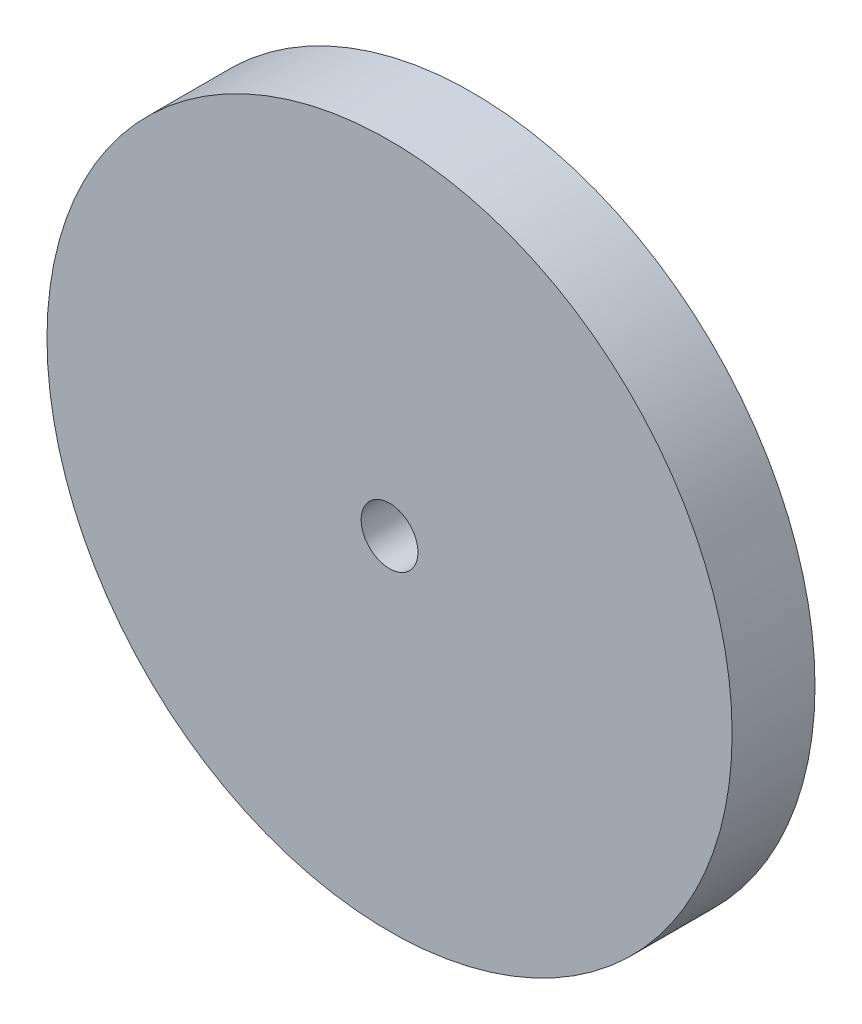
SolidWorks part; units mm, degrees
ref_plane "Front Plane" through (0, 0, 0) normal (0, 0, 1) x (1, 0, 0)
ref_plane "Top Plane" through (0, 0, 0) normal (0, 1, 0) x (1, 0, 0)
ref_plane "Right Plane" through (0, 0, 0) normal (1, 0, 0) x (0, 0, -1)
sketch "Sketch1" plane through (0, 0, 3.175) normal (0, 0, 1) x (1, 0, 0)
  circle A1 centre (-35.5331, 0) radius 24.145
  circle A2 centre (-35.5331, 0) radius 2
  circle A3 centre (-35.5331, 0) radius 24.145 construction
  dimension "D1" = 4
extrude "Boss-Extrude1" add sketch "Sketch1" along normal blind 5.842
